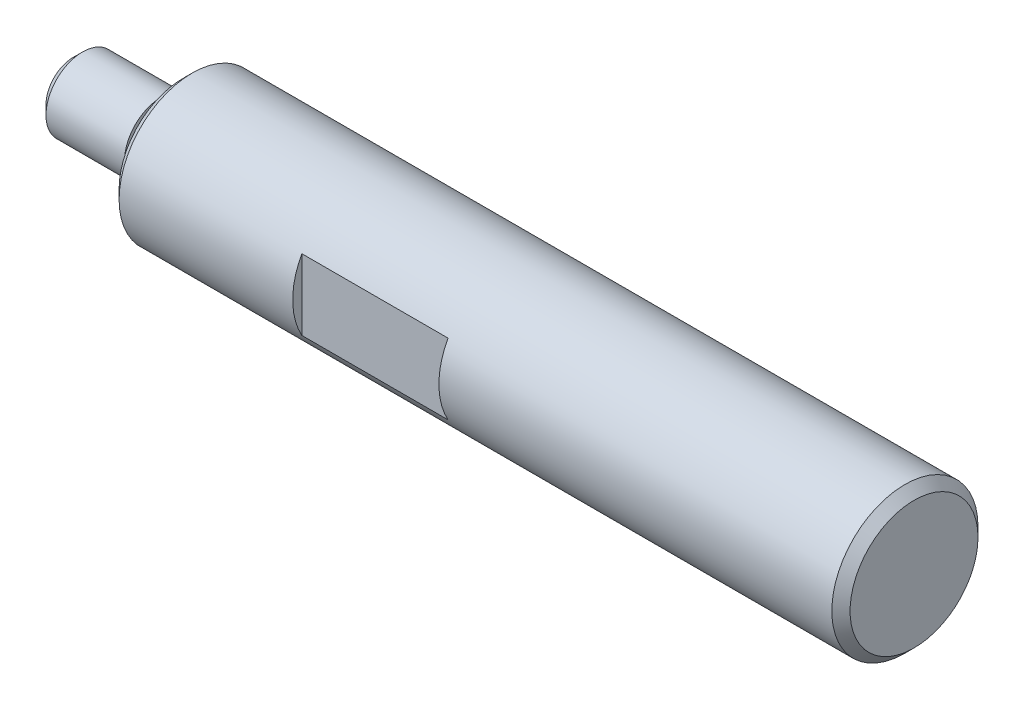
SolidWorks part; units mm, degrees
ref_plane "Front Plane" through (0, 0, 0) normal (0, 0, 1) x (1, 0, 0)
ref_plane "Top Plane" through (0, 0, 0) normal (0, 1, 0) x (1, 0, 0)
ref_plane "Right Plane" through (0, 0, 0) normal (1, 0, 0) x (0, 0, -1)
sketch "Sketch1" plane through (0, 0, 0) normal (0, 0, 1) x (1, 0, 0)
  line L0 (-6, 2) -> (-6, 0)
  line L1 (-6, 0) -> (40, 0)
  line L2 (40, 0) -> (40, 4)
  line L3 (40, 4) -> (0, 4)
  line L4 (0, 4) -> (0, 1.6)
  line L5 (0, 1.6) -> (-1.2, 1.6)
  line L6 (-1.2, 1.6) -> (-1.2, 2)
  line L7 (-1.2, 2) -> (-6, 2)
  line L8 (-6, 0) -> (40, 0) construction
revolve "Revolve1" add sketch "Sketch1" angle 360 about L8 reverse direction yes
ref_plane "Plane1" through (10, 0, 0) normal (-1, 0, 0) x (0, -1, 0)
sketch "Sketch2" plane through (10, 0, 0) normal (-1, 0, 0) x (0, -1, 0)
  line L0 (1.9365, -3.5) -> (-1.9365, -3.5)
  arc A0 (-1.9365, -3.5) -> (1.9365, -3.5) centre (0, 0) ccw
extrude "Cut-Extrude1" cut sketch "Sketch2" against normal blind 8
sketch "Sketch3" plane through (10, 0, 0) normal (-1, 0, 0) x (0, -1, 0)
  line L0 (-1.9365, 3.5) -> (1.9365, 3.5)
  arc A0 (1.9365, 3.5) -> (-1.9365, 3.5) centre (0, 0) ccw
extrude "Cut-Extrude2" cut sketch "Sketch3" against normal blind 8
chamfer "Chamfer1" distance 0.5 angle 45 3 edges at (-6, 0, -2) (40, 0, -4) (0, 0, -4)
ref_axis "Axis1" through (0.5, 0, 0) along (1, 0, 0)
